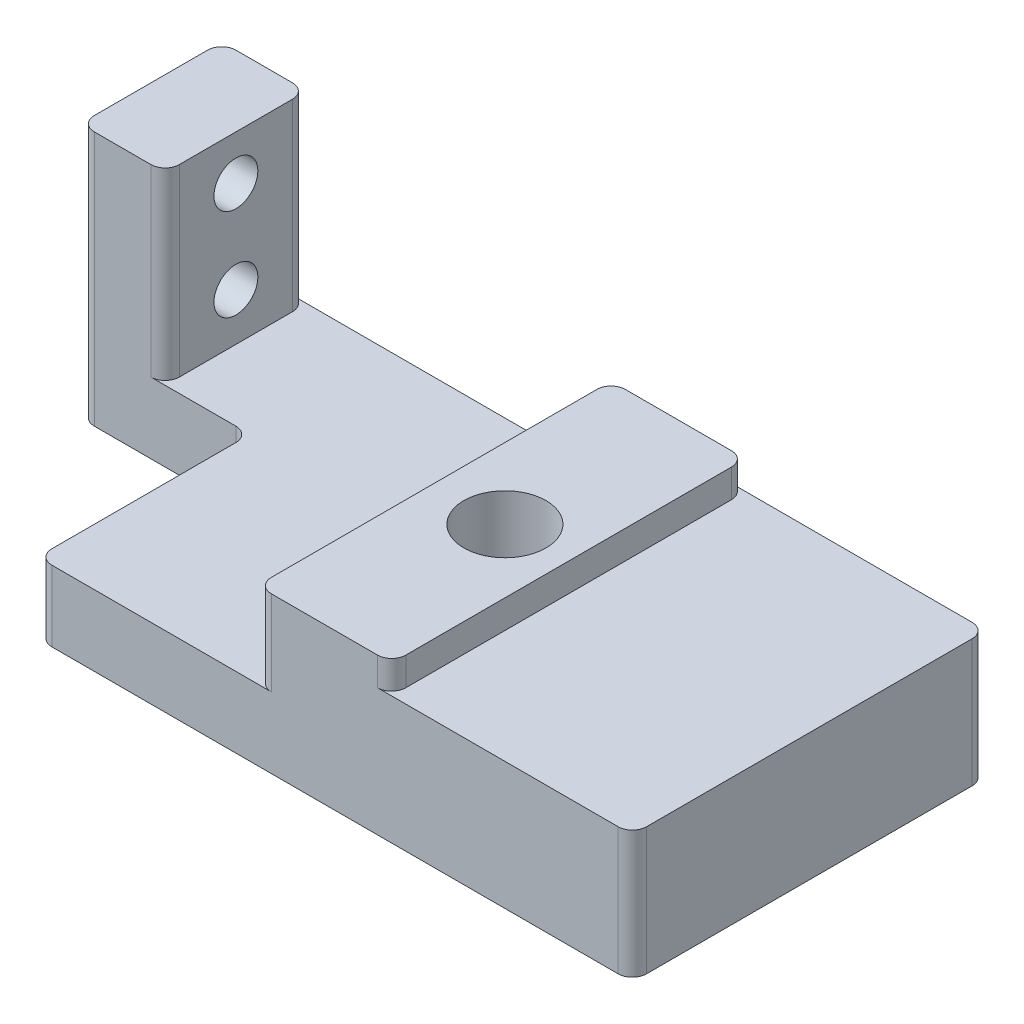
SolidWorks part; units mm, degrees
ref_plane "Front Plane" through (0, 0, 0) normal (0, 0, 1) x (1, 0, 0)
ref_plane "Top Plane" through (0, 0, 0) normal (0, 1, 0) x (1, 0, 0)
ref_plane "Right Plane" through (0, 0, 0) normal (1, 0, 0) x (0, 0, -1)
sketch "Sketch1" plane through (0, 0, 0) normal (0, 1, 0) x (1, 0, 0)
  line L1 (0, 0) -> (45, 0)
  line L2 (0, 0) -> (0, 25)
  line L3 (0, 25) -> (45, 25)
  line L4 (45, 0) -> (45, 25)
  dimension "D1" = 45
  dimension "D2" = 25
extrude "Boss-Extrude1" add sketch "Sketch1" along normal blind 5 contours L1 L4 L3 L2 region at (22.5, 0, -12.5)
sketch "Sketch5" plane through (0, 5, 0) normal (0, 1, 0) x (1, 0, 0)
  line L0 (0, 25) -> (45, 25) construction
  line L1 (18.5, 25) -> (45, 25)
  line L2 (18.5, 25) -> (18.5, 0)
  line L3 (18.5, 0) -> (45, 0)
  line L4 (45, 25) -> (45, 0)
  line L5 (45, 0) -> (45, 25) construction
  line L6 (0, 0) -> (45, 0) construction
  dimension "D1" = 26.5
extrude "Boss-Extrude3" add sketch "Sketch5" along normal blind 4
sketch "Sketch11" plane through (0, 9, 0) normal (0, 1, 0) x (1, 0, 0)
  line L0 (18.5, 25) -> (18.5, 0) construction
  line L1 (18.5, 25) -> (28, 25)
  line L2 (18.5, 25) -> (18.5, 0)
  line L3 (18.5, 0) -> (28, 0)
  line L4 (28, 25) -> (28, 0)
  line L5 (45, 25) -> (18.5, 25) construction
  line L6 (18.5, 0) -> (45, 0) construction
  dimension "D1" = 9.5
extrude "Boss-Extrude5" add sketch "Sketch11" along normal blind 2
sketch "Sketch12" plane through (0, 5, 0) normal (0, 1, 0) x (1, 0, 0)
  line L0 (0, 25) -> (18.5, 25) construction
  line L1 (0, 25) -> (3, 25)
  line L2 (0, 25) -> (0, 0)
  line L3 (0, 0) -> (3, 0)
  line L4 (3, 25) -> (3, 0)
  line L5 (0, 0) -> (0, 25) construction
  line L6 (0, 0) -> (18.5, 0) construction
  dimension "D1" = 3
extrude "Cut-Extrude2" cut sketch "Sketch12" against normal through all
sketch "Sketch13" plane through (0, 0, 0) normal (0, -1, 0) x (-1, 0, 0)
  line L0 (-23.5, 0) -> (-23.5, 25) construction
  line L1 (-3, 0) -> (-45, 0) construction
  line L2 (-3, 25) -> (-45, 25) construction
  line L3 (-45, 0) -> (-45, 25) construction
  point P8 (-23.5, 12.5)
  dimension "D1" = 21.5
hole_wizard "M5 Clearance Hole1" positions "Sketch14" profile "Sketch15" hole size "M5" standard "ISO" end condition through all
sketch "Sketch14" plane through (0, 0, 0) normal (0, -1, 0) x (-1, 0, 0)
  point P0 (-23.5, 12.5)
sketch "Sketch15" plane through (23.5, 0, -12.5) normal (1, 0, 0) x (0, 0, -1)
  line L0 (0, 0) -> (0, 11)
  line L1 (0, 11) -> (2.9, 11)
  line L2 (2.9, 11) -> (2.9, 0)
  line L5 (2.9, 0) -> (0, 0)
  line L11 (0, -6.35) -> (0, 107.95) construction
  dimension "Thru Hole Dia." = 5.8
  dimension "Thru Hole Depth" = 11
sketch "Sketch18" plane through (0, 0, -25) normal (0, 0, -1) x (-1, 0, 0)
  line L0 (-3, 5) -> (-18.5, 5) construction
  line L1 (-3, 0) -> (9, 0)
  line L2 (-3, 0) -> (-3, 5)
  line L3 (-3, 5) -> (3, 5)
  line L7 (9, 0) -> (9, 18)
  line L8 (9, 18) -> (3, 18)
  line L9 (3, 5) -> (3, 18)
  point P11 (0, 0)
  dimension "D1" = 12
  dimension "D2" = 6
  dimension "D3" = 13
extrude "Boss-Extrude8" add sketch "Sketch18" against normal blind 10
sketch "Sketch19" plane through (-9, 0, 0) normal (-1, 0, 0) x (0, 0, 1)
  line L0 (-20, 18) -> (-20, 8.35) construction
  line L1 (-15, 18) -> (-25, 18) construction
  point P1 (-20, 8.35)
  point P4 (-20, 14.85)
  dimension "D1" = 3.15
  dimension "D2" = 6.5
hole_wizard "M2.5 Clearance Hole1" positions "Sketch19" profile "Sketch20" hole size "M2.5" standard "ISO"
sketch "Sketch20" plane through (-9, 14.85, -20) normal (0, 1, 0) x (0, 0, 1)
  line L0 (0, 0) -> (0, 6.9313)
  line L1 (0, 6.9313) -> (1.55, 6)
  line L2 (1.55, 6) -> (1.55, 0)
  line L5 (1.55, 0) -> (0, 0)
  line L10 (0, 6.9313) -> (-1.55, 6) construction
  line L11 (0, -6.35) -> (0, 107.95) construction
  dimension "Hole Dia." = 3.1
  dimension "Hole Depth" = 6
  dimension "Drill Angle" = 118
fillet "Fillet2" radius 1 12 edges at (28, 10, 0) (18.5, 8, 0) (18.5, 8, -25) (28, 10, -25) (3, 2.5, 0) (45, 4.5, 0) (45, 4.5, -25) (-3, 11.5, -25) (-9, 9, -25) (-3, 11.5, -15) (-9, 9, -15) (3, 2.5, -15)
